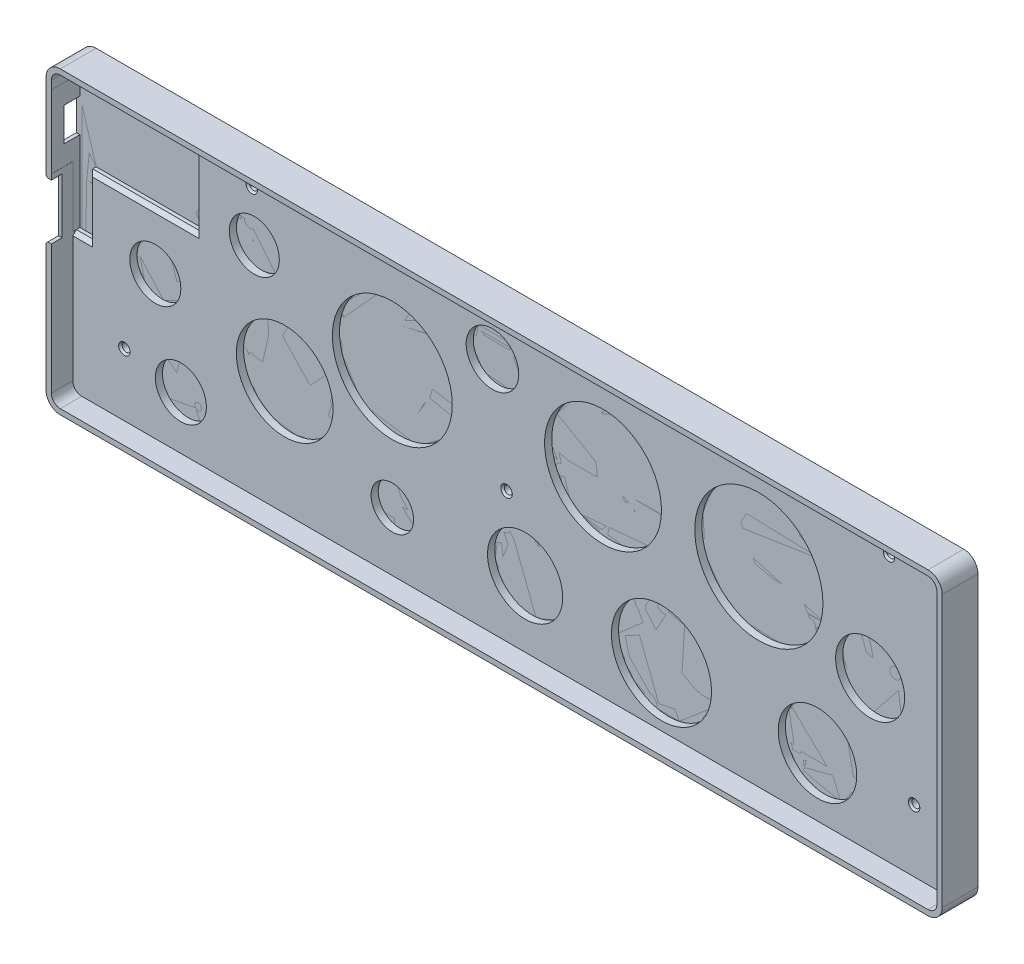
SolidWorks part; units mm, degrees
ref_plane "Front Plane" through (0, 0, 0) normal (0, 0, 1) x (1, 0, 0)
ref_plane "Top Plane" through (0, 0, 0) normal (0, 1, 0) x (1, 0, 0)
ref_plane "Right Plane" through (0, 0, 0) normal (1, 0, 0) x (0, 0, -1)
ref_plane "Plane1" through (0, 0, 1.6) normal (0, 0, 1) x (1, 0, 0)
sketch "Sketch1" plane through (0, 0, 1.6) normal (0, 0, 1) x (1, 0, 0)
  line L0 (342.62, -108.45) -> (99.95, -108.45)
  line L1 (97.95, -110.45) -> (97.95, -186.25)
  line L2 (99.95, -188.25) -> (342.62, -188.25)
  line L3 (344.62, -186.25) -> (344.62, -110.45)
  circle A0 centre (325.72, -114.3) radius 1.1
  circle A1 centre (330.8, -120) radius 0.95
  circle A2 centre (325.72, -120) radius 2.05
  circle A3 centre (320.64, -120) radius 0.95
  circle A4 centre (304.58, -120) radius 0.95
  circle A5 centre (299.5, -120) radius 2.05
  circle A6 centre (294.42, -120) radius 0.95
  circle A7 centre (285.58, -120) radius 0.95
  circle A8 centre (280.5, -120) radius 2.05
  circle A9 centre (329.53, -122.54) radius 1.5
  circle A10 centre (323.18, -125.08) radius 1.5
  circle A11 centre (327.37, -129) radius 0.15
  circle A12 centre (324.07, -129) radius 0.15
  circle A13 centre (303.31, -122.54) radius 1.5
  circle A14 centre (296.96, -125.08) radius 1.5
  circle A15 centre (284.31, -122.54) radius 1.5
  circle A16 centre (301.15, -129) radius 0.15
  circle A17 centre (297.85, -129) radius 0.15
  circle A18 centre (282.15, -129) radius 0.15
  circle A19 centre (275.42, -120) radius 0.95
  circle A20 centre (266.58, -120) radius 0.95
  circle A21 centre (261.5, -120) radius 2.05
  circle A22 centre (256.42, -120) radius 0.95
  circle A23 centre (247.58, -120) radius 0.95
  circle A24 centre (242.5, -120) radius 2.05
  circle A25 centre (237.42, -120) radius 0.95
  circle A26 centre (228.58, -120) radius 0.95
  circle A27 centre (223.5, -120) radius 2.05
  circle A28 centre (265.31, -122.54) radius 1.5
  circle A29 centre (277.96, -125.08) radius 1.5
  circle A30 centre (258.96, -125.08) radius 1.5
  circle A31 centre (278.85, -129) radius 0.15
  circle A32 centre (263.15, -129) radius 0.15
  circle A33 centre (259.85, -129) radius 0.15
  circle A34 centre (246.31, -122.54) radius 1.5
  circle A35 centre (239.96, -125.08) radius 1.5
  circle A36 centre (227.31, -122.54) radius 1.5
  circle A37 centre (220.96, -125.08) radius 1.5
  circle A38 centre (244.15, -129) radius 0.15
  circle A39 centre (240.85, -129) radius 0.15
  circle A40 centre (225.15, -129) radius 0.15
  circle A41 centre (221.85, -129) radius 0.15
  circle A42 centre (333.08, -139) radius 0.95
  circle A43 centre (328, -139) radius 2.05
  circle A44 centre (322.92, -139) radius 0.95
  circle A45 centre (309.33, -139) radius 0.95
  circle A46 centre (304.25, -139) radius 2.05
  circle A47 centre (299.17, -139) radius 0.95
  circle A48 centre (290.33, -139) radius 0.95
  circle A49 centre (285.25, -139) radius 2.05
  circle A50 centre (280.17, -139) radius 0.95
  circle A51 centre (331.81, -141.54) radius 1.5
  circle A52 centre (325.46, -144.08) radius 1.5
  circle A53 centre (329.65, -148) radius 0.15
  circle A54 centre (326.35, -148) radius 0.15
  circle A55 centre (308.06, -141.54) radius 1.5
  circle A56 centre (301.71, -144.08) radius 1.5
  circle A57 centre (289.06, -141.54) radius 1.5
  circle A58 centre (282.71, -144.08) radius 1.5
  circle A59 centre (305.9, -148) radius 0.15
  circle A60 centre (302.6, -148) radius 0.15
  circle A61 centre (286.9, -148) radius 0.15
  circle A62 centre (283.6, -148) radius 0.15
  circle A63 centre (271.33, -139) radius 0.95
  circle A64 centre (266.25, -139) radius 2.05
  circle A65 centre (261.17, -139) radius 0.95
  circle A66 centre (252.33, -139) radius 0.95
  circle A67 centre (247.25, -139) radius 2.05
  circle A68 centre (242.17, -139) radius 0.95
  circle A69 centre (233.33, -139) radius 0.95
  circle A70 centre (228.25, -139) radius 2.05
  circle A71 centre (223.17, -139) radius 0.95
  circle A72 centre (270.06, -141.54) radius 1.5
  circle A73 centre (251.06, -141.54) radius 1.5
  circle A74 centre (263.71, -144.08) radius 1.5
  circle A75 centre (267.9, -148) radius 0.15
  circle A76 centre (264.6, -148) radius 0.15
  circle A77 centre (244.71, -144.08) radius 1.5
  circle A78 centre (232.06, -141.54) radius 1.5
  circle A79 centre (225.71, -144.08) radius 1.5
  circle A80 centre (248.9, -148) radius 0.15
  circle A81 centre (245.6, -148) radius 0.15
  circle A82 centre (229.9, -148) radius 0.15
  circle A83 centre (226.6, -148) radius 0.15
  circle A84 centre (218.42, -120) radius 0.95
  circle A85 centre (209.58, -120) radius 0.95
  circle A86 centre (204.5, -120) radius 2.05
  circle A87 centre (199.42, -120) radius 0.95
  circle A88 centre (190.58, -120) radius 0.95
  circle A89 centre (185.5, -120) radius 2.05
  circle A90 centre (180.42, -120) radius 0.95
  circle A91 centre (171.58, -120) radius 0.95
  circle A92 centre (166.5, -120) radius 2.05
  circle A93 centre (161.42, -120) radius 0.95
  circle A94 centre (208.31, -122.54) radius 1.5
  circle A95 centre (189.31, -122.54) radius 1.5
  circle A96 centre (201.96, -125.08) radius 1.5
  circle A97 centre (206.15, -129) radius 0.15
  circle A98 centre (202.85, -129) radius 0.15
  circle A99 centre (182.96, -125.08) radius 1.5
  circle A100 centre (170.31, -122.54) radius 1.5
  circle A101 centre (163.96, -125.08) radius 1.5
  circle A102 centre (187.15, -129) radius 0.15
  circle A103 centre (183.85, -129) radius 0.15
  circle A104 centre (168.15, -129) radius 0.15
  circle A105 centre (164.85, -129) radius 0.15
  circle A106 centre (147.5, -114.3) radius 1.1
  circle A107 centre (129.49, -115.23) radius 0.5
  circle A108 centre (152.58, -120) radius 0.95
  circle A109 centre (147.5, -120) radius 2.05
  circle A110 centre (142.42, -120) radius 0.95
  circle A111 centre (133.58, -120) radius 0.95
  circle A112 centre (126.95, -115.23) radius 0.5
  circle A113 centre (124.41, -115.23) radius 0.5
  circle A114 centre (121.87, -115.23) radius 0.5
  circle A115 centre (119.33, -115.23) radius 0.5
  circle A116 centre (116.79, -115.23) radius 0.5
  circle A117 centre (114.25, -115.23) radius 0.5
  circle A118 centre (111.71, -115.23) radius 0.5
  circle A119 centre (109.17, -115.23) radius 0.5
  circle A120 centre (106.63, -115.23) radius 0.5
  circle A121 centre (104.09, -115.23) radius 0.5
  circle A122 centre (101.55, -115.23) radius 0.5
  circle A123 centre (128.5, -120) radius 2.05
  circle A124 centre (123.42, -120) radius 0.95
  circle A125 centre (114.58, -120) radius 0.95
  circle A126 centre (120.05, -121.15) radius 0.15
  circle A127 centre (109.5, -120) radius 2.05
  circle A128 centre (104.42, -120) radius 0.95
  circle A129 centre (100.875, -120.825) radius 0.15
  circle A130 centre (151.31, -122.54) radius 1.5
  circle A131 centre (144.96, -125.08) radius 1.5
  circle A132 centre (132.31, -122.54) radius 1.5
  circle A133 centre (149.15, -129) radius 0.15
  circle A134 centre (145.85, -129) radius 0.15
  circle A135 centre (129.49, -130.47) radius 0.5
  circle A136 centre (120.05, -124.45) radius 0.15
  circle A137 centre (125.96, -125.08) radius 1.5
  circle A138 centre (113.31, -122.54) radius 1.5
  circle A139 centre (100.875, -124.125) radius 0.15
  circle A140 centre (106.96, -125.08) radius 1.5
  circle A141 centre (126.95, -130.47) radius 0.5
  circle A142 centre (124.41, -130.47) radius 0.5
  circle A143 centre (121.87, -130.47) radius 0.5
  circle A144 centre (119.33, -130.47) radius 0.5
  circle A145 centre (116.79, -130.47) radius 0.5
  circle A146 centre (114.25, -130.47) radius 0.5
  circle A147 centre (111.71, -130.47) radius 0.5
  circle A148 centre (109.17, -130.47) radius 0.5
  circle A149 centre (106.63, -130.47) radius 0.5
  circle A150 centre (104.09, -130.47) radius 0.5
  circle A151 centre (101.55, -130.47) radius 0.5
  circle A152 centre (214.33, -139) radius 0.95
  circle A153 centre (209.25, -139) radius 2.05
  circle A154 centre (204.17, -139) radius 0.95
  circle A155 centre (195.33, -139) radius 0.95
  circle A156 centre (190.25, -139) radius 2.05
  circle A157 centre (185.17, -139) radius 0.95
  circle A158 centre (176.33, -139) radius 0.95
  circle A159 centre (171.25, -139) radius 2.05
  circle A160 centre (166.17, -139) radius 0.95
  circle A161 centre (213.06, -141.54) radius 1.5
  circle A162 centre (206.71, -144.08) radius 1.5
  circle A163 centre (194.06, -141.54) radius 1.5
  circle A164 centre (210.9, -148) radius 0.15
  circle A165 centre (207.6, -148) radius 0.15
  circle A166 centre (191.9, -148) radius 0.15
  circle A167 centre (175.06, -141.54) radius 1.5
  circle A168 centre (187.71, -144.08) radius 1.5
  circle A169 centre (168.71, -144.08) radius 1.5
  circle A170 centre (188.6, -148) radius 0.15
  circle A171 centre (172.9, -148) radius 0.15
  circle A172 centre (169.6, -148) radius 0.15
  circle A173 centre (157.33, -139) radius 0.95
  circle A174 centre (152.25, -139) radius 2.05
  circle A175 centre (147.17, -139) radius 0.95
  circle A176 centre (138.33, -139) radius 0.95
  circle A177 centre (133.25, -139) radius 2.05
  circle A178 centre (128.17, -139) radius 0.95
  circle A179 centre (116.955, -139) radius 0.95
  circle A180 centre (99.78, -137.775) radius 0.45
  circle A181 centre (111.875, -139) radius 2.05
  circle A182 centre (106.795, -139) radius 0.95
  circle A183 centre (99.78, -140.775) radius 0.45
  circle A184 centre (156.06, -141.54) radius 1.5
  circle A185 centre (149.71, -144.08) radius 1.5
  circle A186 centre (137.06, -141.54) radius 1.5
  circle A187 centre (130.71, -144.08) radius 1.5
  circle A188 centre (153.9, -148) radius 0.15
  circle A189 centre (150.6, -148) radius 0.15
  circle A190 centre (134.9, -148) radius 0.15
  circle A191 centre (131.6, -148) radius 0.15
  circle A192 centre (115.685, -141.54) radius 1.5
  circle A193 centre (109.335, -144.08) radius 1.5
  circle A194 centre (113.525, -148) radius 0.15
  circle A195 centre (110.225, -148) radius 0.15
  circle A196 centre (337.83, -158) radius 0.95
  circle A197 centre (332.75, -158) radius 2.05
  circle A198 centre (327.67, -158) radius 0.95
  circle A199 centre (318.83, -158) radius 0.95
  circle A200 centre (313.75, -158) radius 2.05
  circle A201 centre (308.67, -158) radius 0.95
  circle A202 centre (299.83, -158) radius 0.95
  circle A203 centre (294.75, -158) radius 2.05
  circle A204 centre (289.67, -158) radius 0.95
  circle A205 centre (280.83, -158) radius 0.95
  circle A206 centre (336.56, -160.54) radius 1.5
  circle A207 centre (330.21, -163.08) radius 1.5
  circle A208 centre (317.56, -160.54) radius 1.5
  circle A209 centre (311.21, -163.08) radius 1.5
  circle A210 centre (334.4, -167) radius 0.15
  circle A211 centre (331.1, -167) radius 0.15
  circle A212 centre (315.4, -167) radius 0.15
  circle A213 centre (312.1, -167) radius 0.15
  circle A214 centre (298.56, -160.54) radius 1.5
  circle A215 centre (279.56, -160.54) radius 1.5
  circle A216 centre (292.21, -163.08) radius 1.5
  circle A217 centre (296.4, -167) radius 0.15
  circle A218 centre (293.1, -167) radius 0.15
  circle A219 centre (275.75, -158) radius 2.05
  circle A220 centre (270.67, -158) radius 0.95
  circle A221 centre (261.83, -158) radius 0.95
  circle A222 centre (256.75, -158) radius 2.05
  circle A223 centre (251.67, -158) radius 0.95
  circle A224 centre (242.83, -158) radius 0.95
  circle A225 centre (237.75, -158) radius 2.05
  circle A226 centre (232.67, -158) radius 0.95
  circle A227 centre (223.83, -158) radius 0.95
  circle A228 centre (273.21, -163.08) radius 1.5
  circle A229 centre (260.56, -160.54) radius 1.5
  circle A230 centre (254.21, -163.08) radius 1.5
  circle A231 centre (277.4, -167) radius 0.15
  circle A232 centre (274.1, -167) radius 0.15
  circle A233 centre (258.4, -167) radius 0.15
  circle A234 centre (255.1, -167) radius 0.15
  circle A235 centre (241.56, -160.54) radius 1.5
  circle A236 centre (235.21, -163.08) radius 1.5
  circle A237 centre (222.56, -160.54) radius 1.5
  circle A238 centre (239.4, -167) radius 0.15
  circle A239 centre (236.1, -167) radius 0.15
  circle A240 centre (220.4, -167) radius 0.15
  circle A241 centre (332.75, -171.3) radius 1.1
  circle A242 centre (337.83, -177) radius 0.95
  circle A243 centre (332.75, -177) radius 2.05
  circle A244 centre (327.67, -177) radius 0.95
  circle A245 centre (318.83, -177) radius 0.95
  circle A246 centre (313.75, -177) radius 2.05
  circle A247 centre (308.67, -177) radius 0.95
  circle A248 centre (299.83, -177) radius 0.95
  circle A249 centre (294.75, -177) radius 2.05
  circle A250 centre (289.67, -177) radius 0.95
  circle A251 centre (280.83, -177) radius 0.95
  circle A252 centre (336.56, -179.54) radius 1.5
  circle A253 centre (330.21, -182.08) radius 1.5
  circle A254 centre (317.56, -179.54) radius 1.5
  circle A255 centre (311.21, -182.08) radius 1.5
  circle A256 centre (334.4, -186) radius 0.15
  circle A257 centre (331.1, -186) radius 0.15
  circle A258 centre (315.4, -186) radius 0.15
  circle A259 centre (312.1, -186) radius 0.15
  circle A260 centre (298.56, -179.54) radius 1.5
  circle A261 centre (279.56, -179.54) radius 1.5
  circle A262 centre (292.21, -182.08) radius 1.5
  circle A263 centre (296.4, -186) radius 0.15
  circle A264 centre (293.1, -186) radius 0.15
  circle A265 centre (256.813, -170.015) radius 1.524
  circle A266 centre (275.75, -177) radius 2.05
  circle A267 centre (270.67, -177) radius 0.95
  circle A268 centre (249.955, -177) radius 0.95
  circle A269 centre (232.937, -170.015) radius 1.524
  circle A270 centre (244.875, -177) radius 2.05
  circle A271 centre (239.795, -177) radius 0.95
  circle A272 centre (273.21, -182.08) radius 1.5
  circle A273 centre (277.4, -186) radius 0.15
  circle A274 centre (274.1, -186) radius 0.15
  circle A275 centre (256.813, -185.225) radius 1.9939
  circle A276 centre (248.685, -179.54) radius 1.5
  circle A277 centre (242.335, -182.08) radius 1.5
  circle A278 centre (246.525, -186) radius 0.15
  circle A279 centre (243.225, -186) radius 0.15
  circle A280 centre (232.937, -185.225) radius 1.9939
  circle A281 centre (218.75, -152.3) radius 1.1
  circle A282 centre (218.75, -158) radius 2.05
  circle A283 centre (213.67, -158) radius 0.95
  circle A284 centre (204.83, -158) radius 0.95
  circle A285 centre (199.75, -158) radius 2.05
  circle A286 centre (194.67, -158) radius 0.95
  circle A287 centre (185.83, -158) radius 0.95
  circle A288 centre (180.75, -158) radius 2.05
  circle A289 centre (175.67, -158) radius 0.95
  circle A290 centre (166.83, -158) radius 0.95
  circle A291 centre (161.75, -158) radius 2.05
  circle A292 centre (216.21, -163.08) radius 1.5
  circle A293 centre (203.56, -160.54) radius 1.5
  circle A294 centre (197.21, -163.08) radius 1.5
  circle A295 centre (217.1, -167) radius 0.15
  circle A296 centre (201.4, -167) radius 0.15
  circle A297 centre (198.1, -167) radius 0.15
  circle A298 centre (184.56, -160.54) radius 1.5
  circle A299 centre (178.21, -163.08) radius 1.5
  circle A300 centre (165.56, -160.54) radius 1.5
  circle A301 centre (159.21, -163.08) radius 1.5
  circle A302 centre (182.4, -167) radius 0.15
  circle A303 centre (179.1, -167) radius 0.15
  circle A304 centre (163.4, -167) radius 0.15
  circle A305 centre (160.1, -167) radius 0.15
  circle A306 centre (130.6, -154.325) radius 0.375
  circle A307 centre (156.67, -158) radius 0.95
  circle A308 centre (147.83, -158) radius 0.95
  circle A309 centre (142.75, -158) radius 2.05
  circle A310 centre (137.67, -158) radius 0.95
  circle A311 centre (128.6, -154.325) radius 0.375
  circle A312 centre (121.705, -158) radius 0.95
  circle A313 centre (116.625, -158) radius 2.05
  circle A314 centre (111.545, -158) radius 0.95
  circle A315 centre (146.56, -160.54) radius 1.5
  circle A316 centre (140.21, -163.08) radius 1.5
  circle A317 centre (144.4, -167) radius 0.15
  circle A318 centre (141.1, -167) radius 0.15
  circle A319 centre (120.435, -160.54) radius 1.5
  circle A320 centre (114.085, -163.08) radius 1.5
  circle A321 centre (118.275, -167) radius 0.15
  circle A322 centre (114.975, -167) radius 0.15
  circle A323 centre (209.313, -170.04) radius 1.524
  circle A324 centre (202.455, -177) radius 0.95
  circle A325 centre (197.375, -177) radius 2.05
  circle A326 centre (192.295, -177) radius 0.95
  circle A327 centre (185.437, -170.04) radius 1.524
  circle A328 centre (164.455, -177) radius 0.95
  circle A329 centre (159.375, -177) radius 2.05
  circle A330 centre (201.185, -179.54) radius 1.5
  circle A331 centre (194.835, -182.08) radius 1.5
  circle A332 centre (209.313, -185.25) radius 1.9939
  circle A333 centre (199.025, -186) radius 0.15
  circle A334 centre (195.725, -186) radius 0.15
  circle A335 centre (163.185, -179.54) radius 1.5
  circle A336 centre (185.437, -185.25) radius 1.9939
  circle A337 centre (161.025, -186) radius 0.15
  circle A338 centre (154.295, -177) radius 0.95
  circle A339 centre (140.705, -177) radius 0.95
  circle A340 centre (135.625, -177) radius 2.05
  circle A341 centre (130.545, -177) radius 0.95
  circle A342 centre (111.875, -171.3) radius 1.1
  circle A343 centre (116.955, -177) radius 0.95
  circle A344 centre (111.875, -177) radius 2.05
  circle A345 centre (106.795, -177) radius 0.95
  circle A346 centre (156.835, -182.08) radius 1.5
  circle A347 centre (139.435, -179.54) radius 1.5
  circle A348 centre (133.085, -182.08) radius 1.5
  circle A349 centre (157.725, -186) radius 0.15
  circle A350 centre (137.275, -186) radius 0.15
  circle A351 centre (133.975, -186) radius 0.15
  circle A352 centre (115.685, -179.54) radius 1.5
  circle A353 centre (109.335, -182.08) radius 1.5
  circle A354 centre (113.525, -186) radius 0.15
  circle A355 centre (110.225, -186) radius 0.15
  arc A356 (344.62, -110.45) -> (342.62, -108.45) centre (342.62, -110.45) ccw
  arc A357 (99.95, -108.45) -> (97.95, -110.45) centre (99.95, -110.45) ccw
  arc A358 (97.95, -186.25) -> (99.95, -188.25) centre (99.95, -186.25) ccw
  arc A359 (342.62, -188.25) -> (344.62, -186.25) centre (342.62, -186.25) ccw
extrude "Boss-Extrude1" add sketch "Sketch1" against normal blind 1.6
sketch "Sketch2" plane through (0, 0, 1.6) normal (0, 0, 1) x (1, 0, 0)
  line L5 (99.95, -106.45) -> (342.62, -106.45)
  line L6 (346.62, -110.45) -> (346.62, -186.25)
  line L7 (342.62, -190.25) -> (99.95, -190.25)
  line L8 (95.95, -110.45) -> (95.95, -186.25)
  line L9 (99.95, -107.95) -> (342.62, -107.95)
  line L10 (345.12, -110.45) -> (345.12, -186.25)
  line L11 (342.62, -188.75) -> (99.95, -188.75)
  line L12 (97.45, -186.25) -> (97.45, -110.45)
  circle A0 centre (147.5, -114.3) radius 1.1
  circle A1 centre (325.72, -114.3) radius 1.1
  circle A2 centre (332.75, -171.3) radius 1.1
  circle A3 centre (218.75, -152.3) radius 1.1138
  circle A4 centre (111.875, -171.3) radius 1.106
  arc A9 (95.95, -110.45) -> (99.95, -106.45) centre (99.95, -110.45) cw
  arc A10 (342.62, -106.45) -> (346.62, -110.45) centre (342.62, -110.45) cw
  arc A11 (346.62, -186.25) -> (342.62, -190.25) centre (342.62, -186.25) cw
  arc A12 (99.95, -190.25) -> (95.95, -186.25) centre (99.95, -186.25) cw
  arc A13 (97.45, -110.45) -> (99.95, -107.95) centre (99.95, -110.45) cw
  arc A14 (342.62, -107.95) -> (345.12, -110.45) centre (342.62, -110.45) cw
  arc A15 (345.12, -186.25) -> (342.62, -188.75) centre (342.62, -186.25) cw
  arc A16 (99.95, -188.75) -> (97.45, -186.25) centre (99.95, -186.25) cw
  dimension "D1" = 1.5
extrude "Boss-Extrude2" add sketch "Sketch2" along normal blind 8 and the other way blind 2 separate body contours A12 L7 A11 L6 A10 L5 A9 L8 region at (221.285, -106.7143, 1.6)
sketch "Sketch5" plane through (0, 0, 0) normal (0, 0, 1) x (1, 0, 0)
  line L5 (99.95, -106.45) -> (342.62, -106.45)
  line L6 (346.62, -110.45) -> (346.62, -186.25)
  line L7 (342.62, -190.25) -> (99.95, -190.25)
  line L8 (95.95, -110.45) -> (95.95, -186.25)
  line L9 (99.95, -107.95) -> (342.62, -107.95)
  line L10 (345.12, -110.45) -> (345.12, -186.25)
  line L11 (342.62, -188.75) -> (99.95, -188.75)
  line L12 (97.45, -186.25) -> (97.45, -110.45)
  circle A0 centre (147.5, -114.3) radius 1.1
  circle A1 centre (325.72, -114.3) radius 1.1
  circle A2 centre (332.75, -171.3) radius 1.1
  circle A3 centre (218.75, -152.3) radius 1.1138
  circle A4 centre (111.875, -171.3) radius 1.106
  arc A9 (95.95, -110.45) -> (99.95, -106.45) centre (99.95, -110.45) cw
  arc A10 (342.62, -106.45) -> (346.62, -110.45) centre (342.62, -110.45) cw
  arc A11 (346.62, -186.25) -> (342.62, -190.25) centre (342.62, -186.25) cw
  arc A12 (99.95, -190.25) -> (95.95, -186.25) centre (99.95, -186.25) cw
  arc A13 (97.45, -110.45) -> (99.95, -107.95) centre (99.95, -110.45) cw
  arc A14 (342.62, -107.95) -> (345.12, -110.45) centre (342.62, -110.45) cw
  arc A15 (345.12, -186.25) -> (342.62, -188.75) centre (342.62, -186.25) cw
  arc A16 (99.95, -188.75) -> (97.45, -186.25) centre (99.95, -186.25) cw
  dimension "D1" = 1.5
extrude "Boss-Extrude5" add sketch "Sketch5" along normal blind 2 and the other way blind 2 from offset 1.6 contours A4 A3 A2 A1 A0 region at (221.2795, -148.3534, 0)
sketch "Sketch6" plane through (0, 0, 3.6) normal (0, 0, 1) x (1, 0, 0)
  line L1 (131.7363, -112.7927) -> (99.2016, -112.7927)
  line L2 (131.7363, -112.7927) -> (131.7363, -133.1474)
  line L3 (131.7363, -133.1474) -> (99.2016, -133.1474)
  line L4 (99.2016, -112.7927) -> (99.2016, -133.1474)
extrude "Cut-Extrude1" cut sketch "Sketch6" against normal blind 2
sketch "Sketch7" plane through (99.2016, 0, 0) normal (1, 0, 0) x (0, 0, -1)
  line L0 (-1.6, 96.4207) -> (-1.6, -96.4207) construction
  line L1 (-1.6, -118.2927) -> (-6.1, -118.2927)
  line L2 (-1.6, -118.2927) -> (-1.6, -127.6474)
  line L3 (-1.6, -127.6474) -> (-6.1, -127.6474)
  line L4 (-6.1, -118.2927) -> (-6.1, -127.6474)
  line L5 (-1.6, -112.7927) -> (-1.6, -133.1474)
  line L6 (-1.6, -112.7927) -> (-3.6, -112.7927) construction
  line L7 (-1.6, -112.7927) -> (-1.6, -133.1474) construction
  line L8 (-1.6, -133.1474) -> (-3.6, -133.1474) construction
  line M5 (-3.6, -112.7927) -> (-3.6, -133.1474)
  line M7 (-1.6, -133.1474) -> (-1.6, -112.7927)
  dimension "D1" = 5.5
  dimension "D2" = 5.5
  dimension "D3" = 4.5
extrude "Cut-Extrude2" cut sketch "Sketch7" against normal through all contours L1 L4 L3 M5 | L3 L1 M7 M5 region at (99.2016, -122.9701, 2.6) region at (99.2016, -122.9701, 4.85)
sketch "Sketch8" plane through (0, 0, 3.6) normal (0, 0, 1) x (1, 0, 0)
  line L0 (99.2016, -112.7927) -> (97.4393, -112.7927)
  line L1 (97.4393, -112.7927) -> (97.4393, -133.1546)
  line L2 (97.4393, -133.1546) -> (99.2016, -133.1474)
  line L3 (99.2016, -133.1474) -> (99.2016, -112.7927)
extrude "Cut-Extrude3" cut sketch "Sketch8" against normal blind 2 and the other way blind 10
sketch "Sketch9" plane through (0, 0, 3.6) normal (0, 0, 1) x (1, 0, 0)
  line L0 (99.2016, -133.1474) -> (131.7363, -133.1474) construction
  line L1 (101.9996, -133.1474) -> (97.4393, -133.1474)
  line L2 (101.9996, -133.1474) -> (101.9996, -150.1208)
  line L3 (101.9996, -150.1208) -> (97.4393, -150.1208)
  line L4 (97.4393, -133.1474) -> (97.4393, -150.1208)
extrude "Cut-Extrude4" cut sketch "Sketch9" against normal blind 2
sketch "Sketch11" plane through (97.95, 0, 0) normal (1, 0, 0) x (0, 0, -1)
  line L0 (-3.6, -150.1208) -> (-3.6, -133.1474) construction
  line L1 (-11.6, -150.1138) -> (-6.6, -150.1138)
  line L2 (-11.6, -150.1138) -> (-11.6, -134.6554)
  line L3 (-11.6, -134.6554) -> (-6.6, -134.6554)
  line L4 (-6.6, -150.1138) -> (-6.6, -134.6554)
  dimension "D1" = 3
  dimension "D2" = 5
extrude "Cut-Extrude6" cut sketch "Sketch11" against normal blind 2
chamfer "Chamfer1" distance 0.5 angle 45 3 edges at (95.95, -134.6554, 8.1) (95.95, -142.3846, 6.6) (95.95, -150.1138, 8.1)
chamfer "Chamfer2" distance 0.5 angle 45 4 edges at (95.95, -127.6474, 3.85) (95.95, -122.9701, 1.6) (95.95, -118.2927, 3.85) (95.95, -122.9701, 6.1)
chamfer "Chamfer3" distance 1 angle 45 5 edges at (131.7363, -122.9701, 3.6) (99.7248, -150.1208, 3.6) (101.9996, -141.6341, 3.6) (116.868, -133.1474, 3.6) (114.5932, -112.7927, 3.6)
chamfer "Chamfer4" distance 0.5 angle 45 5 edges at (333.85, -171.3, 3.6) (326.82, -114.3, 3.6) (219.8638, -152.3, 3.6) (148.6, -114.3, 3.6) (112.981, -171.3, 3.6)
sketch "Sketch14" plane through (0, 0, 3.6) normal (0, 0, 1) x (1, 0, 0)
  circle A0 centre (127.6627, -173.9261) radius 7.1409
  circle A1 centre (156.7165, -156.7014) radius 13.5291
  circle A2 centre (186.8079, -139.0617) radius 16.7699
  circle A3 centre (245.7455, -135.3262) radius 16.3473
  circle A4 centre (262.0927, -172.2659) radius 14
  circle A5 centre (186.8079, -172.2659) radius 5.9427
  circle A6 centre (223.9552, -170.2305) radius 10.5147
  circle A7 centre (289.3261, -135.3262) radius 17.9316
  circle A8 centre (305.7207, -172.2659) radius 10.9832
  circle A9 centre (320.4551, -146.7401) radius 9.6539
  circle A10 centre (214.824, -122.2917) radius 7.3564
  circle A11 centre (148.2079, -128.0627) radius 7.0008
  circle A12 centre (120.5219, -148.8154) radius 7.1409
extrude "Cut-Extrude8" cut sketch "Sketch14" against normal blind 2
sketch "Sketch15" plane through (0, 0, -0.4) normal (0, 0, -1) x (-1, 0, 0)
  line L1 (-342.62, -110.45) -> (-99.95, -110.45)
  line L2 (-342.62, -110.45) -> (-342.62, -186.25)
  line L3 (-342.62, -186.25) -> (-99.95, -186.25)
  line L4 (-99.95, -110.45) -> (-99.95, -186.25)
  circle A0 centre (-99.95, -186.25) radius 2
  circle A1 centre (-99.95, -110.45) radius 2
  circle A2 centre (-342.62, -110.45) radius 2
  circle A3 centre (-342.62, -186.25) radius 2
  dimension "D1" = 4
  dimension "D2" = 4
  dimension "D3" = 4
  dimension "D4" = 4
extrude "Cut-Extrude9" cut sketch "Sketch15" against normal blind 1 contours L2 A3 L3 | L3 A3 L2 | L2 A2 L1 | L1 A2 L2 | L4 A1 L1 | L1 A1 L4 | L3 A0 L4 | L4 A0 L3 region at (342.9029, -110.1671, -0.4) region at (341.7712, -111.2988, -0.4) region at (99.6671, -110.1671, -0.4) region at (100.7988, -111.2988, -0.4) region at (341.7712, -185.4012, -0.4) region at (342.9029, -186.5329, -0.4) region at (99.6671, -186.5329, -0.4) region at (100.7988, -185.4012, -0.4)
